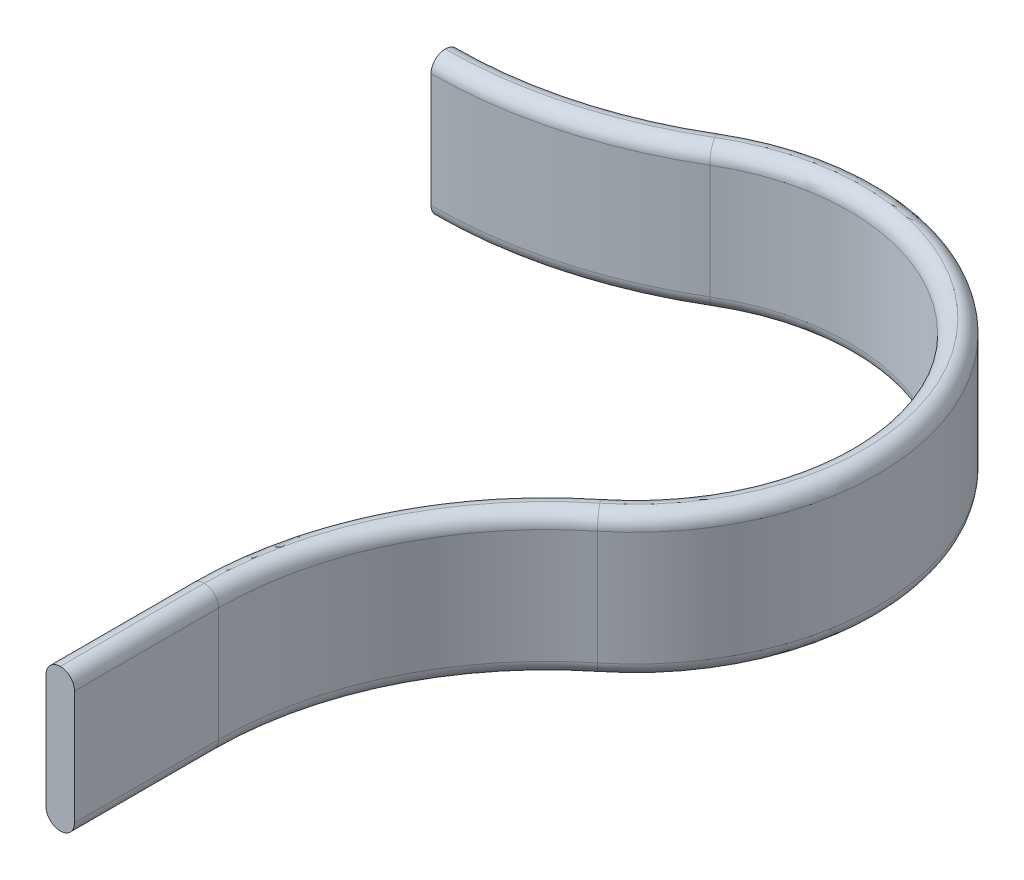
SolidWorks part; units mm, degrees
material "99.5% Aluminum Oxide"
ref_plane "Front Plane" through (0, 0, 0) normal (0, 0, 1) x (1, 0, 0)
ref_plane "Top Plane" through (0, 0, 0) normal (0, 1, 0) x (1, 0, 0)
ref_plane "Right Plane" through (0, 0, 0) normal (1, 0, 0) x (0, 0, -1)
sketch "Sketch1" plane through (0, 0, 0) normal (0, 1, 0) x (1, 0, 0)
  line L0 (0, 0) -> (-46, 0) construction
  line L1 (0, 0) -> (0, -100) construction
  line L2 (4, -79.8063) -> (4, -100)
  line L3 (0, -79.8063) -> (0, -100)
  line L4 (-46, 4) -> (-46, 0)
  line L5 (0, -100) -> (4, -100)
  arc A0 (0, -79.8063) -> (18.75, -40.7751) centre (50, -79.8063) cw
  arc A1 (18.75, -40.7751) -> (-15.3333, 8.4291) centre (0, -17.3563) ccw
  arc A2 (-15.3333, 8.4291) -> (-46, 0) centre (-46, 60) cw
  arc A3 (4, -79.8063) -> (21.25, -43.8976) centre (50, -79.8063) cw
  arc A4 (21.25, -43.8976) -> (-17.3778, 11.8672) centre (0, -17.3563) ccw
  arc A5 (-17.3778, 11.8672) -> (-46, 4) centre (-46, 60) cw
  dimension "D3" = 30
  dimension "D4" = 60
  dimension "D5" = 50
  dimension "D1" = 46
  dimension "D2" = 100
  dimension "D6" = 4
extrude "Boss-Extrude1" add sketch "Sketch1" along normal mid plane 20
fillet "Fillet1" radius 2 16 edges at (0, -10, 89.9031) (4.9306, -10, 58.1557) (24.6613, -10, 0.2736) (4, -10, 89.9031) (8.5362, -10, 59.8877) (27.9495, -10, -2.0041) (0, 10, 89.9031) (4.9306, 10, 58.1557) (24.6613, 10, 0.2736) (4, 10, 89.9031) (8.5362, 10, 59.8877) (27.9495, 10, -2.0041) (-30.098, -10, -2.1456) (-31.1581, -10, -6.0026) (-30.098, 10, -2.1456) (-31.1581, 10, -6.0026)
